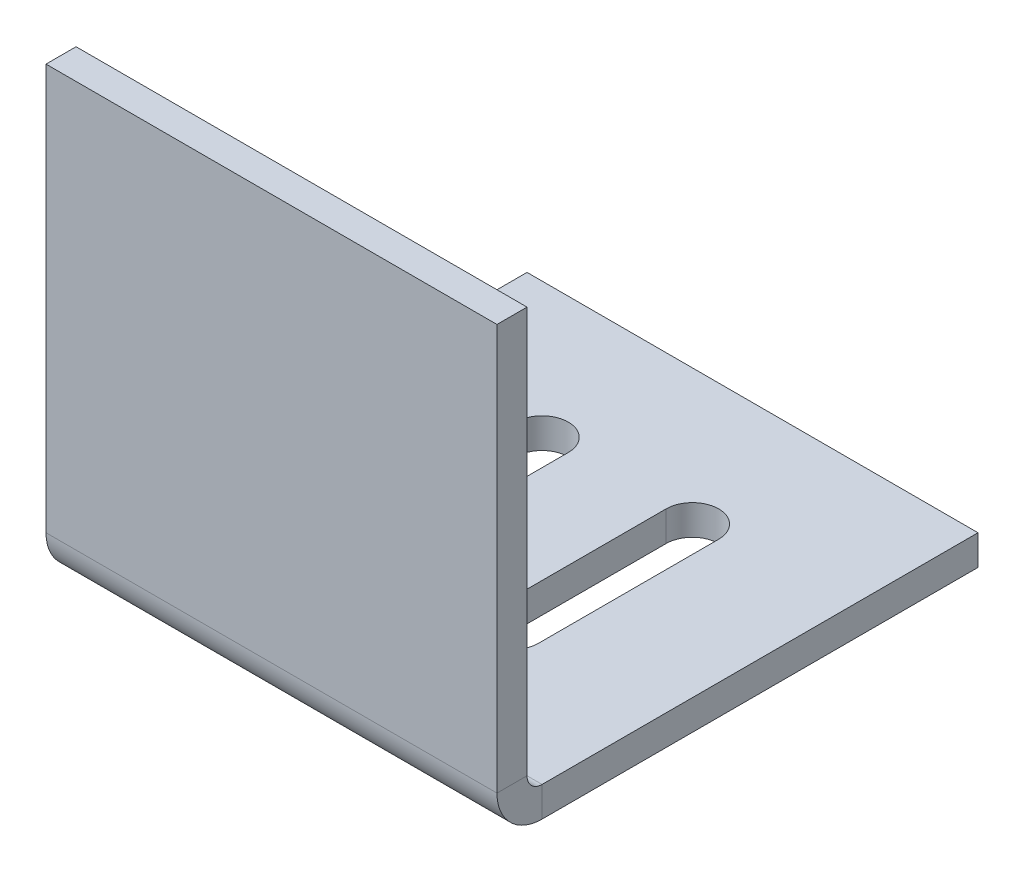
SolidWorks part; units mm, degrees
note: The reader was unsure of these and kept them because the rebuilt part matched: flange length of "Edge-Flange1".
ref_plane "Front" through (0, 0, 0) normal (0, 0, 1) x (1, 0, 0)
ref_plane "Top" through (0, 0, 0) normal (0, 1, 0) x (1, 0, 0)
ref_plane "Right" through (0, 0, 0) normal (1, 0, 0) x (0, 0, -1)
sketch "Sketch1" plane through (0, 0, 0) normal (0, 1, 0) x (1, 0, 0)
  line L0 (-5, -6) -> (-5, 6) construction
  line L1 (15, -15) -> (-15, -15)
  line L2 (15, -15) -> (15, 15)
  line L3 (15, 15) -> (-15, 15)
  line L4 (-15, -15) -> (-15, 15)
  line L5 (15, -15) -> (-15, 15) construction
  line L6 (15, 15) -> (-15, -15) construction
  line L7 (-6.75, -6) -> (-6.75, 6)
  line L8 (-3.25, -6) -> (-3.25, 6)
  line L9 (5, -6) -> (5, 6) construction
  line L10 (3.25, -6) -> (3.25, 6)
  line L11 (6.75, -6) -> (6.75, 6)
  arc A0 (-6.75, -6) -> (-3.25, -6) centre (-5, -6) ccw
  arc A1 (-3.25, 6) -> (-6.75, 6) centre (-5, 6) ccw
  arc A2 (3.25, -6) -> (6.75, -6) centre (5, -6) ccw
  arc A3 (6.75, 6) -> (3.25, 6) centre (5, 6) ccw
  point P0 (0, 0)
  point P6 (-5, 0)
  point P9 (-5, 0)
  point P11 (5, 0)
  point P16 (5, 0)
  dimension "D1" = 30
  dimension "D2" = 30
  dimension "D3" = 5
  dimension "D4" = 5
  dimension "D5" = 3.5
  dimension "D6" = 12
  dimension "D7" = 3.5
  dimension "D8" = 12
  dimension "D9" = 15
  dimension "D10" = 15
sheet metal parameters "Sheet-Metal1" thickness 2 parameters "D1"=1
base flange "Base-Flange1" sketch "Sketch1" thickness 2 reverse thickness direction no parameters "D1"=1
edge flange "Edge-Flange1" sketch "Sketch9" flange angle 90 flange length 30 flange position material outside bend radius 1 thickness 2 relief rectangular parameters "D6"=10
sketch "Sketch9" plane through (0, 0, 15) normal (0, 0, 1) x (1, 0, 0)
  line L0 (-15, 0) -> (15, 0) construction
  line L1 (-15, 0) -> (15, 0)
  line L2 (-15, 0) -> (-15, 28)
  line L3 (-15, 28) -> (15, 28)
  line L4 (15, 28) -> (15, 0)
bend "EdgeBend1" bend radius 1 bend angle 90 parameters "D5"=1
flat pattern "Flat-Pattern1" [suppressed]
sketch "Bend-Lines1" plane through (0, 0, 0) normal (0, 1, 0) x (-1, 0, 0)
sketch3d "Bounding-Box1" [suppressed]
  line L0 (0, 0, 0) -> (0, 30, 0) construction
  line L1 (30, 0, 0) -> (30, 30, 0) construction
  line L2 (0, 0, 0) -> (30, 0, 0) construction
  line L3 (0, 30, 0) -> (30, 30, 0) construction
bend of the flat pattern "Flatten-<EdgeBend1>1"
